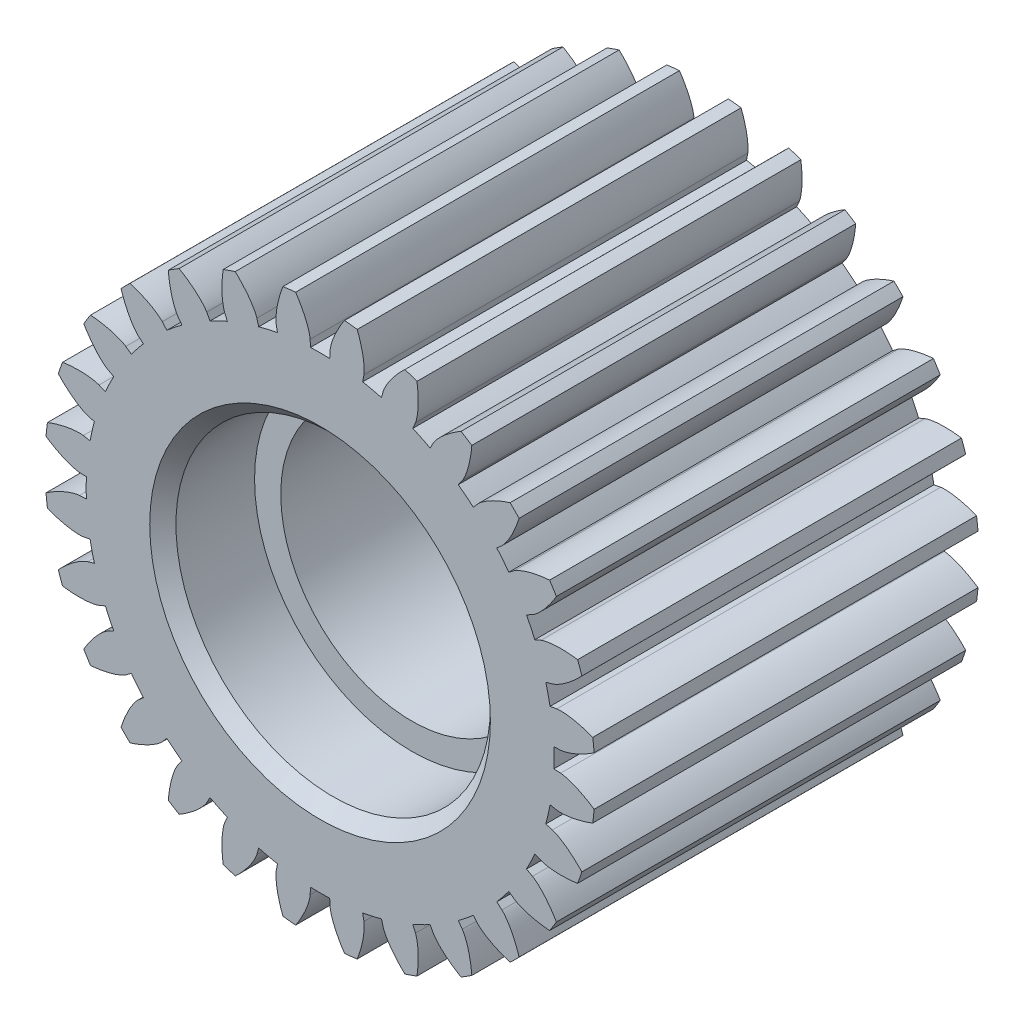
SolidWorks part; units mm, degrees
material "PLA"
ref_plane "Front Plane" through (0, 0, 0) normal (0, 0, 1) x (1, 0, 0)
ref_plane "Top Plane" through (0, 0, 0) normal (0, 1, 0) x (1, 0, 0)
ref_plane "Right Plane" through (0, 0, 0) normal (1, 0, 0) x (0, 0, -1)
sketch "Sketch1" plane through (0, 0, 0) normal (0, 0, 1) x (1, 0, 0)
  circle A0 centre (0, 0) radius 14.7
  dimension "D1" = 29.4
extrude "Boss-Extrude1" add sketch "Sketch1" along normal mid plane 14.6477
sketch "Sketch2" plane through (0, 0, 0) normal (0, 0, 1) x (1, 0, 0)
  line L0 (0, 0) -> (13.9958, 0.3411) construction
  line L1 (0, 0) -> (14, 0) construction
  line L2 (0, 0) -> (13.9958, -0.3411) construction
  line L3 (13.1493, -0.3205) -> (13.1211, -0.3198)
  line L4 (13.1518, 0.3205) -> (13.1211, 0.3198)
  circle A0 centre (0, 0) radius 14 construction
  circle A1 centre (0, 0) radius 13.1557 construction
  circle A2 centre (0, 0) radius 13.125
  circle A3 centre (0, 0) radius 14.7 construction
  circle A4 centre (0, 0) radius 14.7
  spline S0 degree 4 poles (13.1518, 0.3205) (13.1563, 0.3207) (13.1689, 0.3214) (13.1927, 0.3235) (13.2314, 0.328) (13.2806, 0.3354) (13.344, 0.3469) (13.4184, 0.3629) (13.4998, 0.3829) (13.5879, 0.4075) (13.6755, 0.4343) (13.7623, 0.4634) (13.8485, 0.4943) (13.9523, 0.5341) (14.0761, 0.5851) (14.2195, 0.6494) (14.3807, 0.7279) (14.5433, 0.8137) (14.7019, 0.9031) (14.8603, 0.9988) (15.0122, 1.0952) (15.1681, 1.201) (15.3109, 1.3014) (15.4686, 1.4199) (15.5951, 1.5173) (15.7594, 1.6522) (15.8557, 1.7337) (15.9673, 1.8313) (16.0164, 1.8758) (16.0466, 1.9031) knots 0 0 0 0 0 0.005377 0.015084 0.028532 0.04661 0.064855 0.092111 0.119476 0.146842 0.174209 0.201575 0.228941 0.256307 0.307035 0.361767 0.4165 0.471232 0.525964 0.580697 0.635429 0.690161 0.744894 0.799626 0.854358 0.909091 0.954545 1 1 1 1 1 construction
  spline S1 degree 4 poles (13.1518, 0.3205) (13.1563, 0.3207) (13.1689, 0.3214) (13.1927, 0.3235) (13.2314, 0.328) (13.2806, 0.3354) (13.344, 0.3469) (13.4184, 0.3629) (13.4998, 0.3829) (13.5879, 0.4075) (13.6755, 0.4343) (13.7623, 0.4634) (13.8485, 0.4943) (13.9523, 0.5341) (14.0761, 0.5851) (14.2195, 0.6494) (14.3807, 0.7279) (14.5433, 0.8137) (14.7019, 0.9031) (14.8603, 0.9988) (15.0122, 1.0952) (15.1681, 1.201) (15.3109, 1.3014) (15.4686, 1.4199) (15.5951, 1.5173) (15.7238, 1.6229) (15.7861, 1.6751) (15.8178, 1.702) knots 0 0 0 0 0 0.005377 0.015084 0.028532 0.04661 0.064855 0.092111 0.119476 0.146842 0.174209 0.201575 0.228941 0.256307 0.307035 0.361767 0.4165 0.471232 0.525964 0.580697 0.635429 0.690161 0.744894 0.799626 0.854358 0.909091 0.909091 0.909091 0.909091 0.909091
  spline S2 degree 4 poles (13.1493, -0.3205) (13.1538, -0.3206) (13.1664, -0.3213) (13.1902, -0.3234) (13.2289, -0.3279) (13.2781, -0.3354) (13.3415, -0.3469) (13.4159, -0.3628) (13.4973, -0.3829) (13.5855, -0.4074) (13.673, -0.4343) (13.7599, -0.4633) (13.846, -0.4942) (13.9498, -0.534) (14.0736, -0.585) (14.2171, -0.6493) (14.3783, -0.7278) (14.5409, -0.8137) (14.6994, -0.903) (14.8578, -0.9987) (15.0098, -1.0952) (15.1656, -1.2009) (15.3085, -1.3013) (15.4661, -1.4198) (15.5927, -1.5173) (15.757, -1.6521) (15.8532, -1.7337) (15.9649, -1.8312) (16.0139, -1.8757) (16.0442, -1.9031) knots 0 0 0 0 0 0.005377 0.015084 0.028532 0.04661 0.064855 0.092111 0.119476 0.146842 0.174209 0.201575 0.228941 0.256307 0.307035 0.361767 0.4165 0.471232 0.525964 0.580697 0.635429 0.690161 0.744894 0.799626 0.854358 0.909091 0.954545 1 1 1 1 1 construction
  spline S3 degree 4 poles (13.1493, -0.3205) (13.1538, -0.3206) (13.1664, -0.3213) (13.1902, -0.3234) (13.2289, -0.3279) (13.2781, -0.3354) (13.3415, -0.3469) (13.4159, -0.3628) (13.4973, -0.3829) (13.5855, -0.4074) (13.673, -0.4343) (13.7599, -0.4633) (13.846, -0.4942) (13.9498, -0.534) (14.0736, -0.585) (14.2171, -0.6493) (14.3783, -0.7278) (14.5409, -0.8137) (14.6994, -0.903) (14.8578, -0.9987) (15.0098, -1.0952) (15.1656, -1.2009) (15.3085, -1.3013) (15.4661, -1.4198) (15.5927, -1.5173) (15.7214, -1.6229) (15.7837, -1.675) (15.8154, -1.702) knots 0 0 0 0 0 0.005377 0.015084 0.028532 0.04661 0.064855 0.092111 0.119476 0.146842 0.174209 0.201575 0.228941 0.256307 0.307035 0.361767 0.4165 0.471232 0.525964 0.580697 0.635429 0.690161 0.744894 0.799626 0.854358 0.909091 0.909091 0.909091 0.909091 0.909091
  dimension "D1" = 28
  dimension "D2" = 26.3114
  dimension "D3" = 26.25
  dimension "D4" = 1.396
  dimension "D5" = 1.396
extrude "Cut-Extrude1" cut sketch "Sketch2" against normal through all both and the other way through all contours A2 A4 region at (14.0491, -0.0005, 0)
pattern_circular "CirPattern2" count 40 over 360 about axis through (0, 0, 7.3239) along (0, 0, -1) of "Cut-Extrude1"
sketch "Sketch3" plane through (0, 0, 7.3239) normal (0, 0, 1) x (1, 0, 0)
  circle A0 centre (0, 0) radius 5
  dimension "D1" = 10
sketch "Sketch4" plane through (0, 0, -7.3239) normal (0, 0, -1) x (-1, 0, 0)
  circle A0 centre (0, 0) radius 10.5
  dimension "D1" = 21
extrude "Boss-Extrude2" add sketch "Sketch4" along normal blind 14.6477
sketch "Sketch5" plane through (0, 0, -21.9716) normal (0, 0, -1) x (-1, 0, 0)
  line L0 (0, 0) -> (10.5, 0) construction
  line L1 (0, 0) -> (10.4911, 0.4324) construction
  line L2 (0, 0) -> (10.4911, -0.4324) construction
  line L3 (9.1796, 0.3784) -> (8.9174, 0.3676)
  line L4 (9.1796, -0.3784) -> (8.9174, -0.3676)
  circle A0 centre (0, 0) radius 9.209 construction
  circle A1 centre (0, 0) radius 8.925
  arc A2 (10.4584, -0.9339) -> (10.4584, 0.9339) centre (0, 0) ccw
  spline S0 degree 4 poles (9.1796, 0.3784) (9.1827, 0.3785) (9.1915, 0.3792) (9.2082, 0.3809) (9.2352, 0.3846) (9.2853, 0.393) (9.3451, 0.4059) (9.4122, 0.4231) (9.4838, 0.4444) (9.5448, 0.4642) (9.6052, 0.4855) (9.6651, 0.5082) (9.7373, 0.5373) (9.8234, 0.5744) (9.923, 0.6211) (10.0349, 0.678) (10.1477, 0.74) (10.2576, 0.8044) (10.3674, 0.8732) (10.4726, 0.9425) (10.5804, 1.0183) (10.6792, 1.0903) (10.7882, 1.1751) (10.8756, 1.2448) (10.989, 1.3411) (11.0554, 1.3993) (11.1324, 1.4689) (11.1662, 1.5006) (11.187, 1.5201) knots 0 0 0 0 0 0.005377 0.015084 0.028532 0.04661 0.092111 0.119476 0.146842 0.174209 0.201575 0.228941 0.256307 0.307035 0.361767 0.4165 0.471232 0.525964 0.580697 0.635429 0.690161 0.744894 0.799626 0.854358 0.909091 0.954545 1 1 1 1 1 construction
  spline S1 degree 4 poles (9.1796, 0.3784) (9.1827, 0.3785) (9.1915, 0.3792) (9.2082, 0.3809) (9.2352, 0.3846) (9.2853, 0.393) (9.3451, 0.4059) (9.4122, 0.4231) (9.4838, 0.4444) (9.5448, 0.4642) (9.6052, 0.4855) (9.6651, 0.5082) (9.7373, 0.5373) (9.8234, 0.5744) (9.923, 0.6211) (10.0349, 0.678) (10.1477, 0.74) (10.2576, 0.8044) (10.3674, 0.8732) (10.4726, 0.9425) (10.5804, 1.0183) (10.6792, 1.0903) (10.7882, 1.1751) (10.8756, 1.2448) (10.9644, 1.3202) (11.0074, 1.3575) (11.0293, 1.3767) knots 0 0 0 0 0 0.005377 0.015084 0.028532 0.04661 0.092111 0.119476 0.146842 0.174209 0.201575 0.228941 0.256307 0.307035 0.361767 0.4165 0.471232 0.525964 0.580697 0.635429 0.690161 0.744894 0.799626 0.854358 0.909091 0.909091 0.909091 0.909091 0.909091
  spline S2 degree 4 poles (9.1796, -0.3784) (9.1827, -0.3785) (9.1915, -0.3792) (9.2082, -0.3809) (9.2352, -0.3846) (9.2853, -0.393) (9.3451, -0.4059) (9.4122, -0.4231) (9.4838, -0.4444) (9.5448, -0.4642) (9.6052, -0.4855) (9.6651, -0.5082) (9.7373, -0.5373) (9.8234, -0.5744) (9.923, -0.6211) (10.0349, -0.678) (10.1477, -0.74) (10.2576, -0.8044) (10.3674, -0.8732) (10.4726, -0.9425) (10.5804, -1.0183) (10.6792, -1.0903) (10.7882, -1.1751) (10.8756, -1.2448) (10.989, -1.3411) (11.0554, -1.3993) (11.1324, -1.4689) (11.1662, -1.5006) (11.187, -1.5201) knots 0 0 0 0 0 0.005377 0.015084 0.028532 0.04661 0.092111 0.119476 0.146842 0.174209 0.201575 0.228941 0.256307 0.307035 0.361767 0.4165 0.471232 0.525964 0.580697 0.635429 0.690161 0.744894 0.799626 0.854358 0.909091 0.954545 1 1 1 1 1 construction
  spline S3 degree 4 poles (9.1796, -0.3784) (9.1827, -0.3785) (9.1915, -0.3792) (9.2082, -0.3809) (9.2352, -0.3846) (9.2853, -0.393) (9.3451, -0.4059) (9.4122, -0.4231) (9.4838, -0.4444) (9.5448, -0.4642) (9.6052, -0.4855) (9.6651, -0.5082) (9.7373, -0.5373) (9.8234, -0.5744) (9.923, -0.6211) (10.0349, -0.678) (10.1477, -0.74) (10.2576, -0.8044) (10.3674, -0.8732) (10.4726, -0.9425) (10.5804, -1.0183) (10.6792, -1.0903) (10.7882, -1.1751) (10.8756, -1.2448) (10.9644, -1.3202) (11.0074, -1.3575) (11.0293, -1.3767) knots 0 0 0 0 0 0.005377 0.015084 0.028532 0.04661 0.092111 0.119476 0.146842 0.174209 0.201575 0.228941 0.256307 0.307035 0.361767 0.4165 0.471232 0.525964 0.580697 0.635429 0.690161 0.744894 0.799626 0.854358 0.909091 0.909091 0.909091 0.909091 0.909091
  dimension "D2" = 17.85
  dimension "D3" = 21
  dimension "D1" = 18.418
  dimension "D4" = 2.36
  dimension "D5" = 2.36
extrude "Cut-Extrude2" cut sketch "Sketch5" against normal up to surface (14.6477 mm away) contours A2 A1 region at (-9.842, 0, -21.9716) up to face at (10.5, 0, -7.3239)
pattern_circular "CirPattern3" count 28 over 360 about axis through (0, 0, -21.9716) along (0, 0, 1) of "Cut-Extrude2"
extrude "Cut-Extrude3" cut sketch "Sketch3" against normal through all contours A0
sketch "Sketch7" plane through (0, 0, -21.9716) normal (0, 0, -1) x (-1, 0, 0)
  circle A0 centre (0, 0) radius 6
  dimension "D1" = 12
extrude "Cut-Extrude4" cut sketch "Sketch7" against normal blind 3.5
ref_plane "Plane1" through (0, 0, -7.3239) normal (0, 0, -1) x (-1, 0, 0)
mirror "Mirror1" [suppressed] about plane through (0, 0, -7.3239) normal (0, 0, -1)
sketch "Sketch8" plane through (0, 0, 7.3239) normal (0, 0, 1) x (1, 0, 0)
  circle A0 centre (0, 0) radius 50
  dimension "D1" = 100
extrude "Cut-Extrude5" cut sketch "Sketch8" against normal up to surface (14.6477 mm away) up to face at (0, 0, -7.3239)
ref_plane "Plane2" through (0, 0, -14.6477) normal (0, 0, -1) x (-1, 0, 0)
mirror "Mirror3" about plane through (0, 0, -14.6477) normal (0, 0, -1) of "Cut-Extrude4"
chamfer "Chamfer1" distance 0.5 angle 45 2 edges at (-6, 0, -21.9716) (-6, 0, -7.3239)
equation "\"module\" = 0.7"
equation "\"pressure angle\" = 20.0"
equation "\"h_a\" = 0.7"
equation "\"h_b\" = 0.875"
equation "\"clr_tip_root\" = 0.17500000000000004"
equation "\"D1@Sketch1\" = \"dp_p_b\" + 2 * \"h_a\""
equation "\"D1@Boss-Extrude1\"=\"fw_idler\""
equation "\"D1@Sketch2\" = \"dp_p_b\""
equation "\"D2@Sketch2\"= \"db_p_b\""
equation "\"D3@Sketch2\" = \"dp_p_b\" - 2 * \"h_b\""
equation "\"Nr_s\" = 116"
equation "\"pressure_angle\" = 20.0"
equation "\"h_f\" = 0.875"
equation "\"dp_r_s\" = 81.19999999999999"
equation "\"bearing_ID\" = 70"
equation "\"bearing_OD\" = 90"
equation "\"bearing_height\" = 10"
equation "\"clearance_planet\" = 1.5"
equation "\"case_dist\" = 6.5"
equation "\"Motor_case_OD_max\" = 131.3"
equation "\"case_mounting_PCD\" = 123.8"
equation "\"bearing mount thickness\" = 8"
equation "\"case_mounting_hole_dia\" = 3"
equation "\"output_mounting_PCD\" = 98"
equation "\"output_mounting_hole_dia\" = 4"
equation "\"clearance_case_mount_holes_shell_thickness\" = 1"
equation "\"motor_case_OD_base\" = 121.8"
equation "\"sec_carrier_thickness\" = 5"
equation "\"sun_coupler_hub_thickness\" = 4"
equation "\"clearance_sun_coupler_sec_carrier\" = 1.5"
equation "\"clearance_motor_and_case\" = 5"
equation "\"motor_OD\" = 106.8"
equation "\"Motor_case_thickness\" = 2.5"
equation "\"Motor_case_ID\" = 116.8"
equation "\"case_mounting_hole_shift\" = 1.0"
equation "\"output_mounting_nut_wrench_size\" = 7"
equation "\"output_mounting_nut_thickness\" = 3.2"
equation "\"case_mounting_hole_allen_socket_dia\" = 5.5"
equation "\"output_mounting_nut_depth\" = 3"
equation "\"case_mounting_bolt_depth\" = 4.5"
equation "\"Ns\" = 48"
equation "\"ring_radial_thickness\" = 5"
equation "\"ring_to_chamfer_clearance\" = 1.5"
equation "\"Motor_case_OD_base_to_chamfer\" = 5"
equation "\"pattern_offset_from_motor_case_OD_base\" = 3"
equation "\"pattern_bulge_dia\" = 3"
equation "\"pattern_num_bulge\" = 18"
equation "\"pattern_depth\" = 2"
equation "\"motor_height\" = 47.6"
equation "\"case_mounting_wrench_size\" = 5.5"
equation "\"case_mounting_nut_clearance\" = 2"
equation "\"base_plate_thickness\" = 4"
equation "\"case_mounting_nut_thickness\" = 2.4"
equation "\"case_mounting_surface_height\" = 4"
equation "\"motor_mount_hole_PCD\" = 40"
equation "\"motor_mount_hole_dia\" = 5"
equation "\"motor_mount_hole_num\" = 4"
equation "\"central_hole_offset_from_motor_mount_PCD\" = 5"
equation "\"wire_slot_dist_from_center\" = 45.5"
equation "\"wire_slot_length\" = 10"
equation "\"wire_slot_radius\" = 3"
equation "\"driver_upper_holes_dist_from_center\" = 29"
equation "\"driver_lower_holes_dist_from_center\" = 13"
equation "\"driver_side_holes_dist_from_center\" = 22.5"
equation "\"driver_mount_holes_dia\" = 3"
equation "\"driver_mount_inserts_OD\" = 4.8"
equation "\"driver_mount_thickness\" = 1.5"
equation "\"driver_mount_height\" = 6"
equation "\"air_flow_hole_offset\" = 3"
equation "\"num_planet\" = 4"
equation "\"planet_pin_bolt_dia\" = 5"
equation "\"planet_pin_socket_head_dia\" = 8.5"
equation "\"carrier_PCD\" = 61.599999999999994"
equation "\"planet_shaft_dia\" = 8"
equation "\"planet_shaft_step_offset\" = 1"
equation "\"carrier_trapezoidal_support_sun_offset\" = 5"
equation "\"carrier_trapezoidal_support_hole_PCD_offset_bearing_ID\" = 4"
equation "\"carrier_trapezoidal_support_hole_dia\" = 3"
equation "\"carrier_trapezoidal_support_hole_socket_head_dia\" = 5.5"
equation "\"carrier_bearing_step_width\" = 1.5"
equation "\"standard_clearance_1_5mm\" = 1.5"
equation "\"standard_fillet_1_5mm\" = 1.5"
equation "\"sun_shaft_bearing_OD\" = 16"
equation "\"sun_shaft_bearing_width\" = 5"
equation "\"standard_bearing_insertion_chamfer\" = 0.5"
equation "\"carrier_trapezoidal_support_hole_wrench_size\" = 5.5"
equation "\"planet_pin_bolt_wrench_size\" = 8"
equation "\"planet_bearing_OD\" = 12"
equation "\"planet_bearing_width\" = 3.5"
equation "\"planet_bore\" = 10"
equation "\"D1@Sketch3\"=\"planet_bore\""
equation "\"Np_b\" = 40"
equation "\"dp_s\" = 33.599999999999994"
equation "\"db_s\" = 31.57367205840652"
equation "\"fw_s_calc\" = 5.685933367726717"
equation "\"alpha_s\" = 0.8539582918412343"
equation "\"beta_s\" = 2.0420834163175314"
equation "\"dp_p_b\" = 28.0"
equation "\"db_p_b\" = 26.311393382005434"
equation "\"fw_p_s\" = 25.912913082891553"
equation "\"alpha_p_b\" = 0.8539582918412485"
equation "\"beta_p_b\" = 2.792083416317503"
equation "\"motor_output_hole_PCD\" = 23"
equation "\"motor_output_hole_dia\" = 4"
equation "\"motor_output_hole_num\" = 4"
equation "\"sun_shaft_bearing_ID\" = 8"
equation "\"sun_hub_dia\" = 30.0"
equation "\"sun_central_bolt_dia\" = 5"
equation "\"sun_central_bolt_socket_head_dia\" = 8.5"
equation "\"fw_s_used\" = 63.40868620995457"
equation "\"motor_output_hole_CSK_OD\" = 8"
equation "\"motor_output_hole_CSK_head_height\" = 2.0"
equation "\"bearing_retainer_thickness\" = 2"
equation "\"Np_s\" = 28"
equation "\"fw_p_b\" = 29.99577312706301"
equation "\"dp_p_s\" = 19.599999999999998"
equation "\"db_p_s\" = 18.417975367403802"
equation "\"alpha_p_s\" = 0.8539582918412592"
equation "\"beta_p_s\" = 4.7206548448889105"
equation "\"D1@Sketch4\"=\"dp_p_s\" + 2 * \"h_a\""
equation "\"D1@Boss-Extrude2\"=\"fw_idler\""
equation "\"D2@Sketch5\"=\"dp_p_s\" - 2 * \"h_b\""
equation "\"D3@Sketch5\"=\"dp_p_s\"+2 * \"h_a\" "
equation "\"D1@Sketch5\"=\"db_p_s\""
equation "\"D1@CirPattern3\"=\"Np_s\""
equation "\"D4@Sketch5\"=\"beta_p_s\"/2"
equation "\"D5@Sketch5\"=\"beta_p_s\"/2"
equation "\"D4@Sketch2\"=\"beta_p_b\"/2"
equation "\"D5@Sketch2\"=\"beta_p_b\"/2"
equation "\"D1@Sketch7\"=\"planet_bearing_OD\""
equation "\"D1@Cut-Extrude4\"=\"planet_bearing_width\""
equation "\"D1@Chamfer1\"=\"standard_bearing_insertion_chamfer\""
equation "\"D1@CirPattern2\"=\"Np_b\""
equation "\"Nr_b\" = 128"
equation "\"dp_r_b\" = 89.6"
equation "\"db_r_b\" = 84.19645882241738"
equation "\"fw_r_b\" = 29.99577312706301"
equation "\"alpha_r_b\" = 0.8539582918412556"
equation "\"beta_r_b\" = 3.114166583682511"
equation "\"ring_OD_b\" = 99.6"
equation "\"Fillet10\"= IIF ( \"ring_OD_b\" > ( \"bearing_OD\" + 2 * \"bearing mount thickness\" ) , \"suppressed\" , \"unsuppressed\" )"
equation "\"Fillet11\"= IIF ( \"ring_OD_b\" < ( \"bearing_OD\" + 2 * \"bearing mount thickness\" ) , \"suppressed\" , \"unsuppressed\" )"
equation "\"clr_tip_root_s\" = 0.17500000000000004"
equation "\"db_r_s\" = 76.30304080781575"
equation "\"fw_r_s\" = 24.412913082891553"
equation "\"alpha_r_s\" = 0.8539582918412556"
equation "\"beta_r_s\" = 3.259640721613546"
equation "\"small_ring_case_thickness\" = 4"
equation "\"carrier_thickness\" = 4"
equation "\"small_ring_output_wall_thickness\" = 5"
equation "\"small_ring_output_wall_to_bearing_shaft_attachement_hole_dia\" = 4"
equation "\"small_ring_output_wall_to_bearing_shaft_attachement_hole_depth\" = 6.5"
equation "\"small_ring_output_wall_to_bearing_shaft_attachement_nut_wrench\" = 7"
equation "\"small_ring_output_wall_to_bearing_shaft_attachement_nut_thickness\" = 3.2"
equation "\"small_ring_output_wall_to_bearing_shaft_attachement_hole_pcd\" = 12"
equation "\"small_ring_output_wall_to_bearing_shaft_attachement_hole_num\" = 3"
equation "\"small_ring_output_wall_to_bearing_shaft_attachement_hole_CSK_OD\" = 8"
equation "\"small_ring_output_wall_to_bearing_shaft_attachement_hole_CSK_head_height\" = 2.0"
equation "\"carrier_small_ring_inner_bearing_ID\" = 20"
equation "\"carrier_small_ring_inner_bearing_OD\" = 32"
equation "\"carrier_small_ring_inner_bearing_height\" = 7"
equation "\"carrier_small_ring_inner_bearing_flap\" = 2"
equation "\"gear_casing_big_ring_to_bearing_dist\" = 34.91291308289155"
equation "\"gear_casing_thickness\" = 4"
equation "\"tight_clearance_3DP\" = 0.4"
equation "\"loose_clearance_3DP\" = 0.8"
equation "\"Ns_fs\" = 60"
equation "\"dp_fs\" = 42.0"
equation "\"db_fs\" = 39.46709007300815"
equation "\"alpha_fs\" = 0.8539582918412592"
equation "\"beta_fs\" = 1.2920834163174817"
equation "\"fw_fs\" = 25.912913082891553"
equation "\"num_idler\" = 4"
equation "\"idler_angle_offset\" = 45.0"
equation "\"fs_bore_dia\" = 31.599999999999998"
equation "\"fs_bore_wall\" = 2.6500000000000004"
equation "\"fs_axial_clearance\" = 0.8"
equation "\"fw_idler\" = 14.647747849734928"
